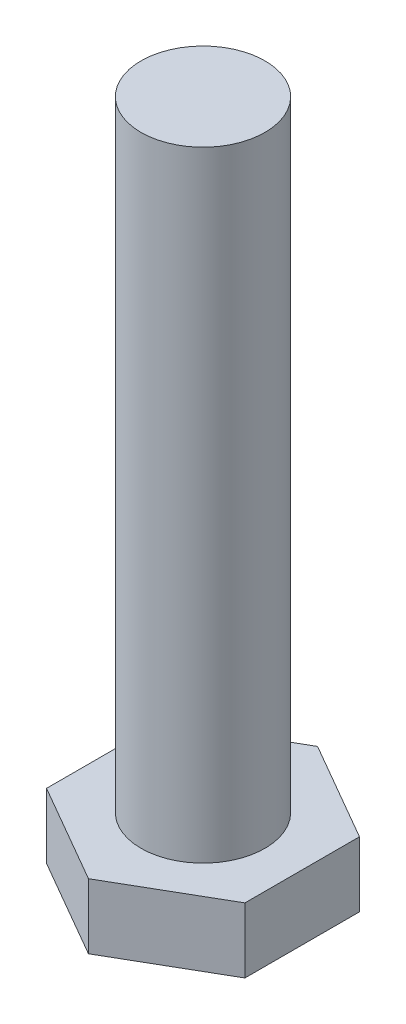
SolidWorks part; units mm, degrees
ref_plane "Спереди" through (0, 0, 0) normal (0, 0, 1) x (1, 0, 0)
ref_plane "Сверху" through (0, 0, 0) normal (0, 1, 0) x (1, 0, 0)
ref_plane "Справа" through (0, 0, 0) normal (1, 0, 0) x (0, 0, -1)
sketch "Эскиз1" plane through (0, 0, 0) normal (0, 1, 0) x (1, 0, 0)
  line L1 (4, -2.3094) -> (4, 2.3094)
  line L2 (4, 2.3094) -> (0, 4.6188)
  line L3 (0, 4.6188) -> (-4, 2.3094)
  line L4 (-4, 2.3094) -> (-4, -2.3094)
  line L5 (-4, -2.3094) -> (0, -4.6188)
  line L6 (0, -4.6188) -> (4, -2.3094)
  circle A0 centre (0, 0) radius 4 construction
extrude "Бобышка-Вытянуть1" add sketch "Эскиз1" along normal blind 3.2
sketch "Эскиз2" plane through (0, 3.2, 0) normal (0, 1, 0) x (1, 0, 0)
  circle A0 centre (0, 0) radius 2.5
extrude "Бобышка-Вытянуть2" add sketch "Эскиз2" along normal blind 25
chamfer "Фаска1" distance 1 angle 30 6 edges at (2, 0, -3.4641) (4, 0, 0) (2, 0, 3.4641) (-2, 0, 3.4641) (-4, 0, 0) (-2, 0, -3.4641) first distance on face at (0, 0, 0)
